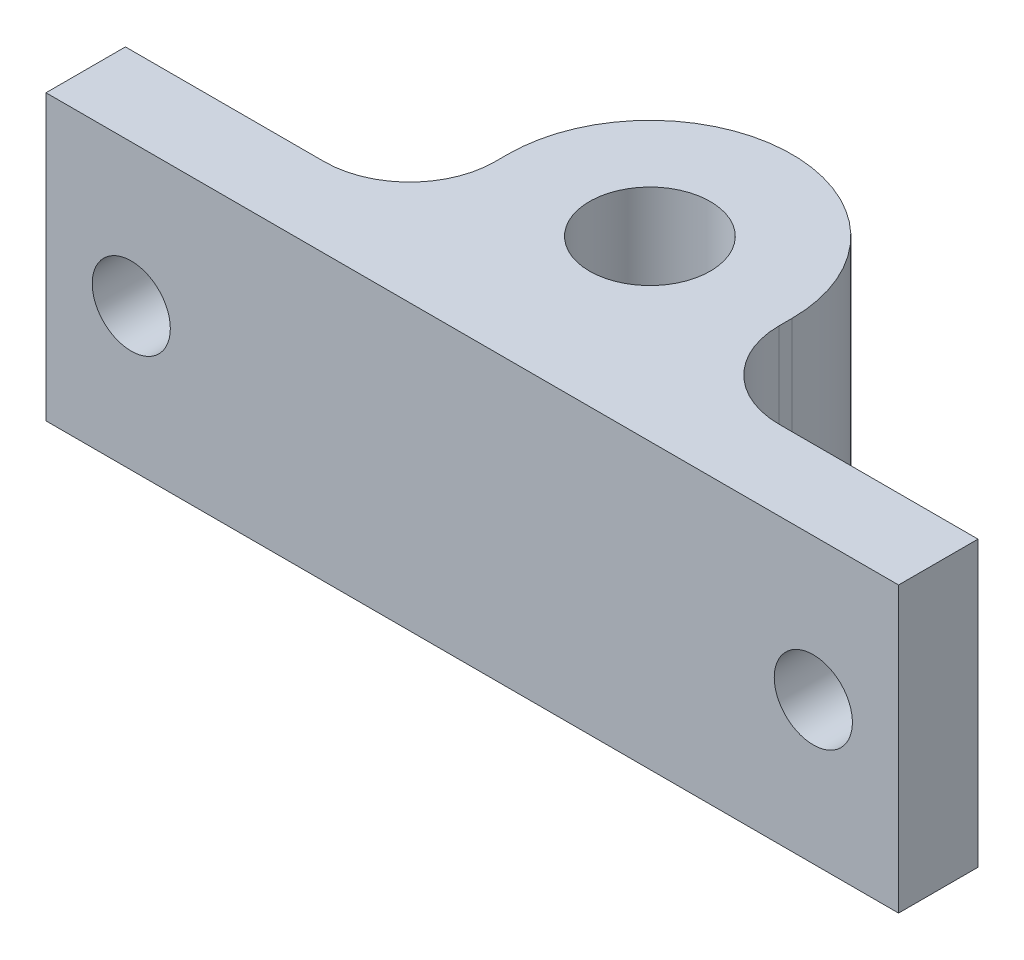
SolidWorks part; units mm, degrees
ref_plane "Front Plane" through (0, 0, 0) normal (0, 0, 1) x (1, 0, 0)
ref_plane "Top Plane" through (0, 0, 0) normal (0, 1, 0) x (1, 0, 0)
ref_plane "Right Plane" through (0, 0, 0) normal (1, 0, 0) x (0, 0, -1)
sketch "Sketch1" plane through (0, 0, 0) normal (0, 1, 0) x (1, 0, 0)
  line L0 (30, -12.5) -> (-30, -12.5)
  line L5 (-30, -12.5) -> (-30, -6.9096)
  line L7 (0, -47.9589) -> (0, -6.9096) construction
  line L8 (30, -12.5) -> (30, -6.9096)
  line L10 (-30, -6.9096) -> (-16, -6.9096)
  line L11 (-10, 0) -> (-10, -0.9096)
  line L12 (10, 0) -> (10, -0.9096)
  line L13 (16, -6.9096) -> (30, -6.9096)
  line L14 (0, -4.25) -> (0, 12.5) construction
  circle A0 centre (0, 0) radius 4.25
  arc A2 (10, 0) -> (-10, 0) centre (0, 0) ccw
  arc A3 (10, -0.9096) -> (16, -6.9096) centre (16, -0.9096) ccw
  arc A4 (-10, -0.9096) -> (-16, -6.9096) centre (-16, -0.9096) cw
  point P17 (10, -6.9096)
  dimension "D1" = 8.5
  dimension "D2" = 12.5
  dimension "D4" = 20
  dimension "D5" = 6
  dimension "D3" = 60
extrude "Boss-Extrude1" add sketch "Sketch1" along normal blind 20
sketch "Sketch2" plane through (0, 0, 6.9096) normal (0, 0, -1) x (-1, 0, 0)
  line L0 (-30, 10) -> (30, 10) construction
  line L1 (-30, 20) -> (-30, 0) construction
  line L2 (30, 20) -> (30, 0) construction
  line L3 (0, 0) -> (0, 20) construction
  line L4 (-10, 0) -> (10, 0) construction
  line L5 (10, 20) -> (-10, 20) construction
  circle A0 centre (-24, 10) radius 2.75
  circle A1 centre (24, 10) radius 2.75
  dimension "D1" = 5.5
  dimension "D2" = 6
extrude "Cut-Extrude1" cut sketch "Sketch2" against normal through all
